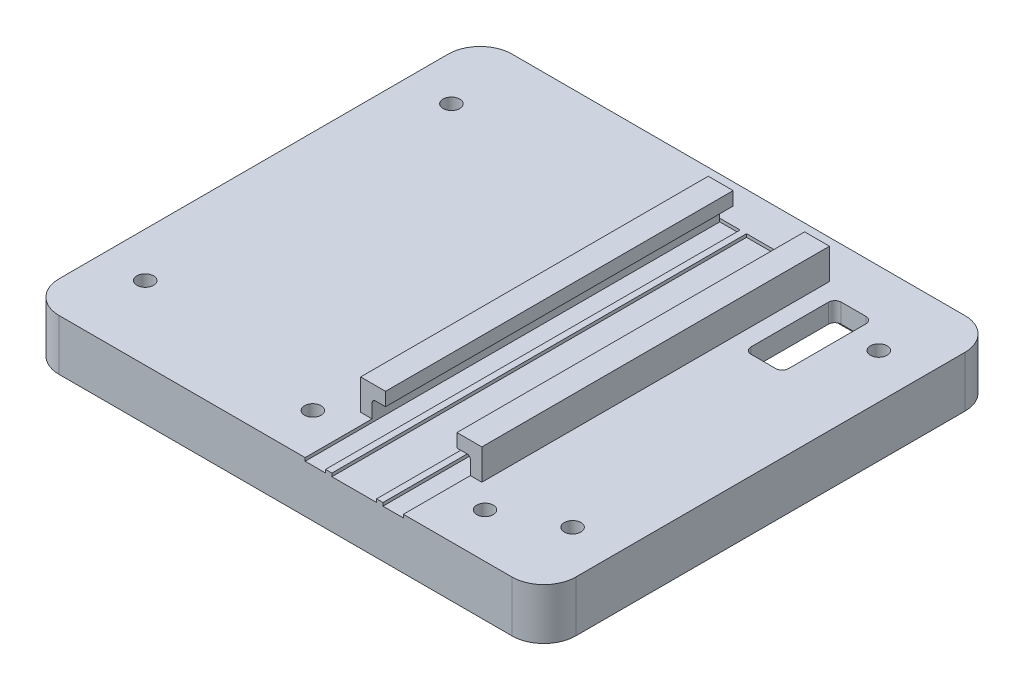
SolidWorks part; units mm, degrees
ref_plane "Alzado" through (0, 0, 0) normal (0, 0, 1) x (1, 0, 0)
ref_plane "Planta" through (0, 0, 0) normal (0, 1, 0) x (1, 0, 0)
ref_plane "Vista lateral" through (0, 0, 0) normal (1, 0, 0) x (0, 0, -1)
sketch "Croquis9" plane through (0, 0, 0) normal (0, 0, 1) x (1, 0, 0)
  line L0 (0, 17.7123) -> (0, -23.4478) construction
  line L1 (0, 10.708) -> (-22, 10.708)
  line L2 (-22, 10.708) -> (-22, 7.708)
  line L3 (-22, 7.708) -> (-19, 7.708)
  line L4 (-19, 7.708) -> (-4.5, 6.708)
  line L5 (-4.5, 6.708) -> (-4.5, -8.292)
  line L6 (-4.5, -8.292) -> (0, -8.292)
  line L7 (0, 10.708) -> (0, -8.292)
  dimension "D1" = 22
  dimension "D2" = 4.5
  dimension "D3" = 3
  dimension "D4" = 1
  dimension "D5" = 15
  dimension "D6" = 3
  dimension "D7" = 19
revolve "Revolución3" add sketch "Croquis9" angle 360 about L0
sketch "Croquis17" plane through (0, 0, 0) normal (1, 0, 0) x (0, 0, -1)
  line L0 (-4.5, -8.292) -> (4.5, -8.292) construction
  circle A0 centre (0, -2.292) radius 1.5
  dimension "D1" = 3
  dimension "D2" = 6
extrude "Cortar-Extruir7" cut sketch "Croquis17" along normal up to next
sketch "Croquis18" plane through (0, 10.708, 0) normal (0, 1, 0) x (1, 0, 0)
  line L0 (1, 2.9343) -> (1, -2.9343)
  arc A0 (1, 2.9343) -> (1, -2.9343) centre (0, 0) ccw
  dimension "D1" = 6.2
  dimension "D2" = 1
extrude "Cortar-Extruir10" cut sketch "Croquis18" against normal blind 5 from offset 3 offset against normal yes
sketch "Croquis21" plane through (0, 0, 0) normal (0, 0, 1) x (1, 0, 0)
  line L0 (0, 3.5811) -> (0, -1.3759) construction
  line L1 (0, 1.8085) -> (-3.1, 1.8085)
  line L2 (-3.1, 1.8085) -> (-3.1, -1.6716)
  line L3 (-3.1, -1.6716) -> (0, -1.6716)
  line L4 (0, 1.8085) -> (0, -1.6716)
  dimension "D1" = 3.1
revolve "Cortar-Revolución1" cut sketch "Croquis21" angle 360 about L0
chamfer "Chaflán1" [suppressed] distance 0.5 angle 45
sketch "Croquis22" plane through (0, 10.708, 0) normal (0, 1, 0) x (1, 0, 0)
  line L1 (-37.5, -32.5) -> (37.5, -32.5)
  line L2 (-37.5, -32.5) -> (-37.5, 32.5)
  line L3 (-37.5, 32.5) -> (37.5, 32.5)
  line L4 (37.5, -32.5) -> (37.5, 32.5)
  line L5 (-37.5, -32.5) -> (37.5, 32.5) construction
  line L6 (-37.5, 32.5) -> (37.5, -32.5) construction
  point P0 (0, 0)
  dimension "D1" = 65
  dimension "D2" = 75
extrude "Saliente-Extruir1" add sketch "Croquis22" against normal up to surface (3 mm away) up to face at (0, 7.708, 19)
fillet "Redondeo1" radius 2 4 edges at (-37.5, 9.208, -32.5) (37.5, 9.208, -32.5) (37.5, 9.208, 32.5) (-37.5, 9.208, 32.5)
sketch "Croquis23" plane through (0, 10.708, 0) normal (0, 1, 0) x (1, 0, 0)
  circle A0 centre (-33.5, 24) radius 1.3
  circle A1 centre (-33.5, -24) radius 1.3
  circle A2 centre (33.5, -24) radius 1.3
  circle A3 centre (33.5, 24) radius 1.3
  dimension "D1" = 2.6
  dimension "D4" = 48
  dimension "D3" = 33.5
  dimension "D2" = 67
  dimension "D5" = 24
extrude "Cortar-Extruir11" cut sketch "Croquis23" against normal blind 2
sketch "Croquis24" plane through (0, 10.708, 0) normal (0, 1, 0) x (1, 0, 0)
  line L0 (6.27, -32.5) -> (6.27, -36.5)
  line L1 (3.27, 29.5) -> (18.27, 29.5)
  line L2 (3.27, 29.5) -> (3.27, -32.5)
  line L3 (3.27, -32.5) -> (18.27, -32.5)
  line L4 (18.27, 29.5) -> (18.27, -32.5)
  line L5 (6.27, 29.5) -> (7.27, 29.5)
  line L6 (6.27, 29.5) -> (6.27, -32.5)
  line L7 (6.27, -32.5) -> (7.27, -32.5)
  line L8 (7.27, 29.5) -> (7.27, -32.5)
  line L9 (14.27, 29.5) -> (15.27, 29.5)
  line L10 (14.27, 29.5) -> (14.27, -32.5)
  line L11 (14.27, -32.5) -> (15.27, -32.5)
  line L12 (15.27, 29.5) -> (15.27, -32.5)
  line L13 (35.5, 32.5) -> (-35.5, 32.5) construction
  line L14 (-35.5, -32.5) -> (35.5, -32.5) construction
  line L15 (3.27, -32.5) -> (18.27, -32.5)
  line L16 (3.27, -32.5) -> (3.27, -36.5)
  line L17 (3.27, -36.5) -> (18.27, -36.5)
  line L18 (18.27, -32.5) -> (18.27, -36.5)
  line L19 (6.27, -36.5) -> (7.27, -36.5)
  line L20 (7.27, -36.5) -> (7.27, -32.5)
  line L21 (14.27, -32.5) -> (14.27, -36.5)
  line L22 (15.27, -32.5) -> (15.27, -36.5)
  dimension "D1" = 3
  dimension "D2" = 15
  dimension "D3" = 1
  dimension "D4" = 1
  dimension "D5" = 3.27
  dimension "D6" = 3
  dimension "D7" = 3
  dimension "D8" = 4
extrude "Cortar-Extruir12" cut sketch "Croquis24" against normal blind 0.5 contours L6 L1 L2 L3 | L10 L1 L8 L3 | L1 L12 L3 L4 region at (4.77, 10.708, 1.5) region at (10.77, 10.708, 1.5) region at (16.77, 10.708, 1.5)
sketch "Croquis25" plane through (0, 10.708, 0) normal (0, 1, 0) x (1, 0, 0)
  line L0 (3.27, 29.5) -> (3.27, -32.5) construction
  line L1 (18.27, 29.5) -> (18.27, -32.5) construction
  line L3 (-35.5, -32.5) -> (3.27, -32.5) construction
  circle A0 centre (-2.73, -28.5) radius 1.3
  circle A1 centre (24.27, -28.5) radius 1.3
  circle A2 centre (33.5, -24) radius 1.3 construction
  circle A3 centre (33.5, -24) radius 1.3 construction
  dimension "D2" = 6
  dimension "D1" = 6
  dimension "D4" = 4
extrude "Cortar-Extruir13" cut sketch "Croquis25" against normal blind 2
sketch "Croquis26" plane through (0, 10.708, 0) normal (0, 1, 0) x (1, 0, 0)
  line L1 (22.988, 27.6308) -> (28.8765, 27.6308)
  line L2 (22.988, 27.6308) -> (22.988, 13.4757)
  line L3 (22.988, 13.4757) -> (28.8765, 13.4757)
  line L4 (28.8765, 27.6308) -> (28.8765, 13.4757)
extrude "Cortar-Extruir14" cut sketch "Croquis26" against normal blind 10
sketch "Croquis30" plane through (0, 0, 32.5) normal (0, 0, 1) x (1, 0, 0)
  line L0 (3.27, 10.708) -> (1.27, 10.708)
  line L1 (1.27, 10.708) -> (1.27, 15.508)
  line L2 (1.27, 15.508) -> (5.17, 15.508)
  line L3 (5.17, 15.508) -> (5.17, 13.408)
  line L4 (5.17, 13.408) -> (3.27, 13.408)
  line L5 (3.27, 13.408) -> (3.27, 10.708)
  line L6 (18.27, 10.708) -> (20.27, 10.708)
  line L7 (18.27, 10.708) -> (35.5, 10.708) construction
  line L8 (20.27, 10.708) -> (20.27, 15.508)
  line L9 (20.27, 15.508) -> (16.37, 15.508)
  line L10 (16.37, 15.508) -> (16.37, 13.408)
  line L11 (16.37, 13.408) -> (18.27, 13.408)
  line L12 (18.27, 13.408) -> (18.27, 10.708)
  dimension "D1" = 1.9
  dimension "D2" = 4.8
  dimension "D3" = 2
  dimension "D4" = 2.7
extrude "Saliente-Extruir2" add sketch "Croquis30" against normal up to surface (62 mm away) from offset 7.5 up to face at (4.77, 10.458, -29.5) offset against normal yes
sketch "Croquis31" plane through (0, 0, 32.5) normal (0, 0, 1) x (1, 0, 0)
  line L0 (3.27, 13.408) -> (5.17, 13.408) construction
  line L1 (3.27, 10.208) -> (3.07, 10.208)
  line L2 (3.27, 10.208) -> (3.27, 13.408)
  line L3 (3.27, 13.408) -> (3.07, 13.408)
  line L4 (3.07, 10.208) -> (3.07, 13.408)
  line L5 (18.27, 10.208) -> (18.47, 10.208)
  line L6 (18.27, 10.208) -> (18.27, 13.408)
  line L7 (18.27, 13.408) -> (18.47, 13.408)
  line L8 (18.47, 10.208) -> (18.47, 13.408)
  line L9 (16.37, 13.408) -> (18.27, 13.408) construction
  dimension "D1" = 0.2
  dimension "D2" = 0.2
extrude "Cortar-Extruir17" cut sketch "Croquis31" against normal up to surface (62 mm away) and the other way blind 10 up to face at (4.77, 10.458, -29.5)
fillet "Redondeo2" radius 0.5 2 edges at (18.47, 13.408, -2.25) (3.07, 13.408, -2.25)
fillet "Redondeo3" radius 1 4 edges at (28.8765, 9.208, -13.4757) (22.988, 9.208, -13.4757) (22.988, 9.208, -27.6308) (28.8765, 9.208, -27.6308)
sketch "Croquis33" plane through (0, 10.708, 0) normal (0, 1, 0) x (1, 0, 0)
  circle A1 centre (-33.5, -24) radius 2.6
  circle A2 centre (-33.5, 24) radius 2.6
  circle A3 centre (-2.73, -28.5) radius 2.6
  circle A4 centre (24.27, -28.5) radius 2.6
  circle A5 centre (33.5, -24) radius 2.6
  circle A6 centre (33.5, 24) radius 2.6
  dimension "D1" = 5.2
extrude "Saliente-Extruir3" add sketch "Croquis33" against normal blind 5 from surface starting at face at (25.9322, 7.708, -20.5533)
sketch "Croquis34" plane through (0, 10.708, 0) normal (0, 1, 0) x (1, 0, 0)
  circle A0 centre (-33.5, -24) radius 1.3 construction
  circle A1 centre (-2.73, -28.5) radius 1.3 construction
  circle A2 centre (24.27, -28.5) radius 1.3 construction
  circle A3 centre (33.5, -24) radius 1.3 construction
  circle A4 centre (33.5, 24) radius 1.3 construction
  circle A5 centre (-33.5, 24) radius 1.3 construction
  circle A6 centre (-33.5, -24) radius 1.3
  circle A7 centre (-2.73, -28.5) radius 1.3
  circle A8 centre (24.27, -28.5) radius 1.3
  circle A9 centre (33.5, -24) radius 1.3
  circle A10 centre (33.5, 24) radius 1.3
  circle A11 centre (-33.5, 24) radius 1.3
extrude "Cortar-Extruir18" cut sketch "Croquis34" against normal through all
ref_axis "Eje1" through (33.5, 2.708, -24) along (0, 1, 0)
ref_plane "Plano1" through (0, 0, -24) normal (0, 0, -1) x (-1, 0, 0)
sketch "Croquis37" plane through (0, 0, -24) normal (0, 0, -1) x (-1, 0, 0)
  line L0 (-30.9, 5.208) -> (-29.9, 7.708)
  line L1 (-30.9, 2.708) -> (-30.9, 7.708) construction
  line L2 (-35.5, 7.708) -> (35.5, 7.708) construction
  dimension "D1" = 1
  dimension "D2" = 2.5
rib "Nervio3" sketch "Croquis37" sketch "Croquis37" thickness 1.8 extrusion direction parallel to sketch draft on no parameters "D1"=1.8
pattern_circular "MatrizC3" count 4 every 90 about axis through (33.5, 2.708, -24) along (0, 1, 0) of "Nervio3"
pattern_linear "MatrizL3" count 2 spacing 67.1 along (-1, 0, 0) count 2 spacing 48 along (0, 0, 1) of "MatrizC3"
sketch "Croquis38" plane through (0, 7.708, 0) normal (0, -1, 0) x (1, 0, 0)
  line L24 (37.5, 30.5) -> (37.5, -30.5) construction
  line L25 (35.5, -32.5) -> (-35.5, -32.5) construction
  line L26 (-35.5, 32.5) -> (35.5, 32.5) construction
  line L27 (-37.5, -30.5) -> (-37.5, 30.5) construction
  line L28 (-40.5, 30.5) -> (-40.5, -30.5)
  line L29 (-35.5, -35.5) -> (35.5, -35.5)
  line L30 (40.5, -30.5) -> (40.5, 30.5)
  line L31 (35.5, 35.5) -> (-35.5, 35.5)
  line L32 (-40.5, 30.5) -> (-40.5, -30.5)
  line L33 (-35.5, -35.5) -> (35.5, -35.5)
  line L34 (40.5, -30.5) -> (40.5, 30.5)
  line L35 (35.5, 35.5) -> (-35.5, 35.5)
  line L36 (37.5, 30.5) -> (37.5, -30.5)
  line L37 (35.5, -32.5) -> (-35.5, -32.5)
  line L38 (-35.5, 32.5) -> (35.5, 32.5)
  line L39 (-37.5, -30.5) -> (-37.5, 30.5)
  arc A18 (37.5, 30.5) -> (35.5, 32.5) centre (35.5, 30.5) ccw construction
  arc A19 (35.5, -32.5) -> (37.5, -30.5) centre (35.5, -30.5) ccw construction
  arc A20 (-37.5, -30.5) -> (-35.5, -32.5) centre (-35.5, -30.5) ccw construction
  arc A21 (-35.5, 32.5) -> (-37.5, 30.5) centre (-35.5, 30.5) ccw construction
  arc A22 (-35.5, 35.5) -> (-40.5, 30.5) centre (-35.5, 30.5) ccw
  arc A23 (-40.5, -30.5) -> (-35.5, -35.5) centre (-35.5, -30.5) ccw
  arc A24 (35.5, -35.5) -> (40.5, -30.5) centre (35.5, -30.5) ccw
  arc A25 (40.5, 30.5) -> (35.5, 35.5) centre (35.5, 30.5) ccw
  arc A26 (-35.5, 35.5) -> (-40.5, 30.5) centre (-35.5, 30.5) ccw
  arc A27 (-40.5, -30.5) -> (-35.5, -35.5) centre (-35.5, -30.5) ccw
  arc A28 (35.5, -35.5) -> (40.5, -30.5) centre (35.5, -30.5) ccw
  arc A29 (40.5, 30.5) -> (35.5, 35.5) centre (35.5, 30.5) ccw
  arc A30 (37.5, 30.5) -> (35.5, 32.5) centre (35.5, 30.5) ccw
  arc A31 (35.5, -32.5) -> (37.5, -30.5) centre (35.5, -30.5) ccw
  arc A32 (-37.5, -30.5) -> (-35.5, -32.5) centre (-35.5, -30.5) ccw
  arc A33 (-35.5, 32.5) -> (-37.5, 30.5) centre (-35.5, 30.5) ccw
  dimension "D1" = 3
extrude "Saliente-Extruir4" add sketch "Croquis38" along normal blind 5 and the other way up to surface (3 mm away) other way up to face at (-33.5, 10.708, 25.3)
sketch "Croquis39" plane through (0, -8.292, 0) normal (0, -1, 0) x (1, 0, 0)
  circle A0 centre (0, 0) radius 3.1
  dimension "D1" = 6.2
extrude "Cortar-Extruir19" cut sketch "Croquis39" against normal blind 11
sketch "Croquis41" plane through (0, 10.708, 0) normal (0, 1, 0) x (1, 0, 0)
  line L0 (35.5, -35.5) -> (-35.5, -35.5) construction
  line L1 (3.07, -32.5) -> (6.27, -32.5)
  line L2 (3.07, -32.5) -> (3.07, -35.5)
  line L3 (3.07, -35.5) -> (6.27, -35.5)
  line L4 (6.27, -32.5) -> (6.27, -35.5)
  line L5 (18.47, -32.5) -> (15.27, -32.5) construction
  line L6 (7.27, -32.5) -> (14.27, -32.5)
  line L7 (7.27, -32.5) -> (7.27, -35.5)
  line L8 (7.27, -35.5) -> (14.27, -35.5)
  line L9 (14.27, -32.5) -> (14.27, -35.5)
  line L10 (15.27, -32.5) -> (18.47, -32.5)
  line L11 (15.27, -32.5) -> (15.27, -35.5)
  line L12 (15.27, -35.5) -> (18.47, -35.5)
  line L13 (18.47, -32.5) -> (18.47, -35.5)
extrude "Cortar-Extruir20" cut sketch "Croquis41" against normal up to surface (0.5 mm away) up to face at (10.77, 10.208, 1.5)
